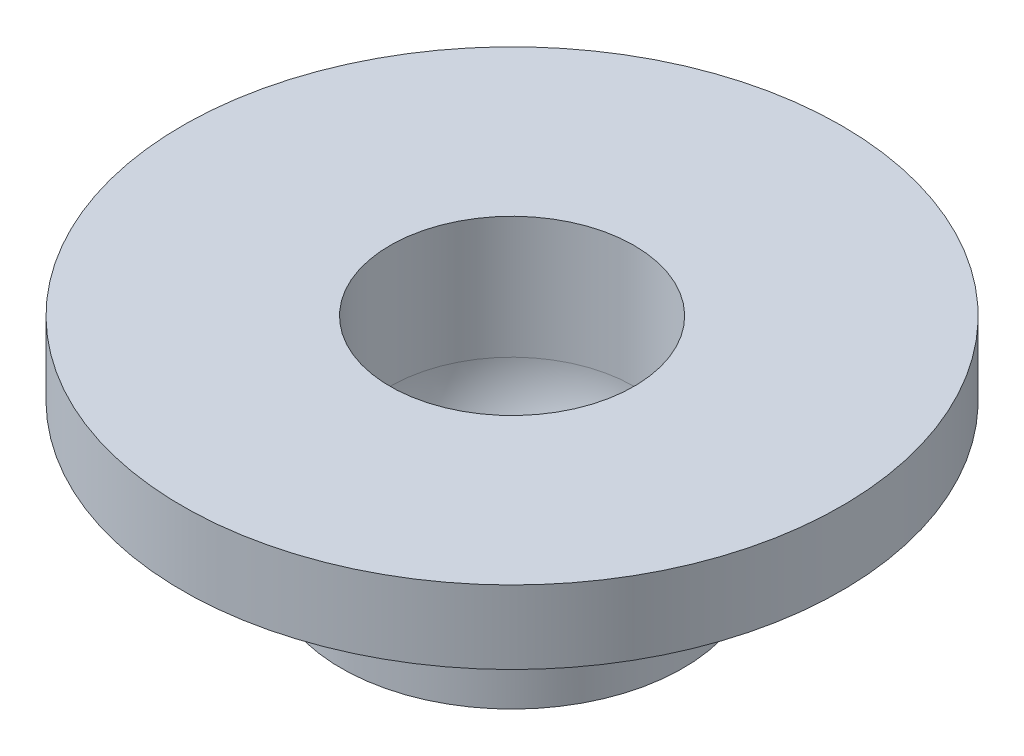
SolidWorks part; units mm, degrees
ref_plane "Front Plane" through (0, 0, 0) normal (0, 0, 1) x (1, 0, 0)
ref_plane "Top Plane" through (0, 0, 0) normal (0, 1, 0) x (1, 0, 0)
ref_plane "Right Plane" through (0, 0, 0) normal (1, 0, 0) x (0, 0, -1)
sketch "Sketch1" plane through (0, 0, 0) normal (1, 0, 0) x (0, 0, -1)
  line L0 (-13.5, 5) -> (-5, 5)
  line L1 (-13.5, 5) -> (-13.5, 2)
  line L2 (0, 0) -> (0, 10.3505) construction
  line L3 (-13.5, 2) -> (-7, 2)
  line L4 (-5, 0) -> (-5, 5)
  line L6 (-7, -4) -> (-3, -4)
  line L7 (-7, -4) -> (-7, 2)
  arc A0 (-5, 0) -> (-3, -4) centre (0, 0) ccw
  dimension "D1" = 13.5
  dimension "D2" = 5
  dimension "D4" = 3
  dimension "D5" = 6.5
  dimension "D6" = 4
revolve "Revolve1" add sketch "Sketch1" angle 360 about L2
fillet "Fillet2" radius 2 1 edges at (0, 2, -7)
